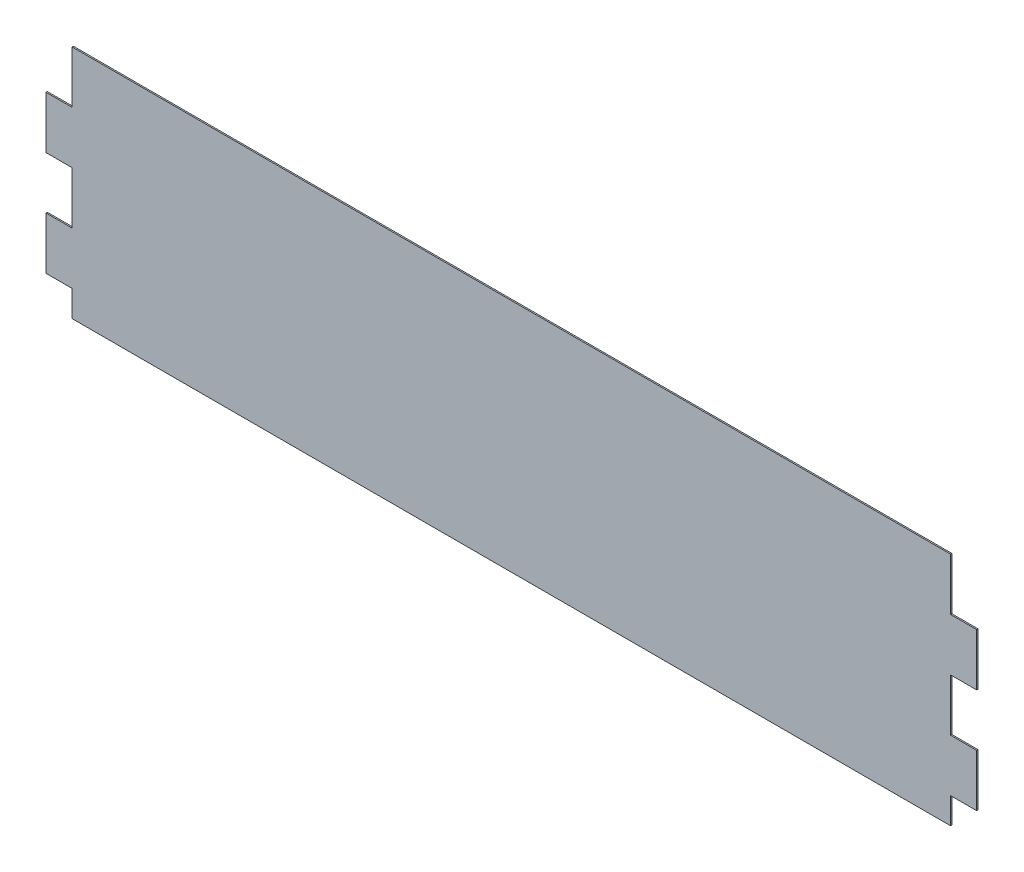
SolidWorks part; units mm, degrees
ref_plane "Front Plane" through (0, 0, 0) normal (0, 0, 1) x (1, 0, 0)
ref_plane "Top Plane" through (0, 0, 0) normal (0, 1, 0) x (1, 0, 0)
ref_plane "Right Plane" through (0, 0, 0) normal (1, 0, 0) x (0, 0, -1)
sketch "Sketch2" plane through (0, 0, 0) normal (0, 0, 1) x (1, 0, 0)
  line L0 (0, 0) -> (5, 0)
  line L1 (5, 0) -> (173, 0)
  line L2 (173, 0) -> (178, 0)
  line L3 (178, 0) -> (178, 45)
  line L4 (178, 45) -> (0, 45)
  line L5 (0, 45) -> (0, 0)
  dimension "D1" = 45
  dimension "D2" = 5
  dimension "D3" = 5
  dimension "D4" = 168
  dimension "D5" = 45
extrude "Boss-Extrude1" add sketch "Sketch2" along normal mid plane 0.25
sketch "Sketch3" plane through (0, 0, 0.125) normal (0, 0, 1) x (1, 0, 0)
  line L1 (0, 45) -> (5, 45)
  line L2 (0, 45) -> (0, 35)
  line L3 (0, 35) -> (5, 35)
  line L4 (5, 45) -> (5, 35)
  dimension "D1" = 5
  dimension "D2" = 10
extrude "Cut-Extrude1" cut sketch "Sketch3" against normal through all
pattern_linear "LPattern2" count 4 spacing 20 along (0, -1, 0) count 2 spacing 173 along (1, 0, 0) of "Cut-Extrude1"
